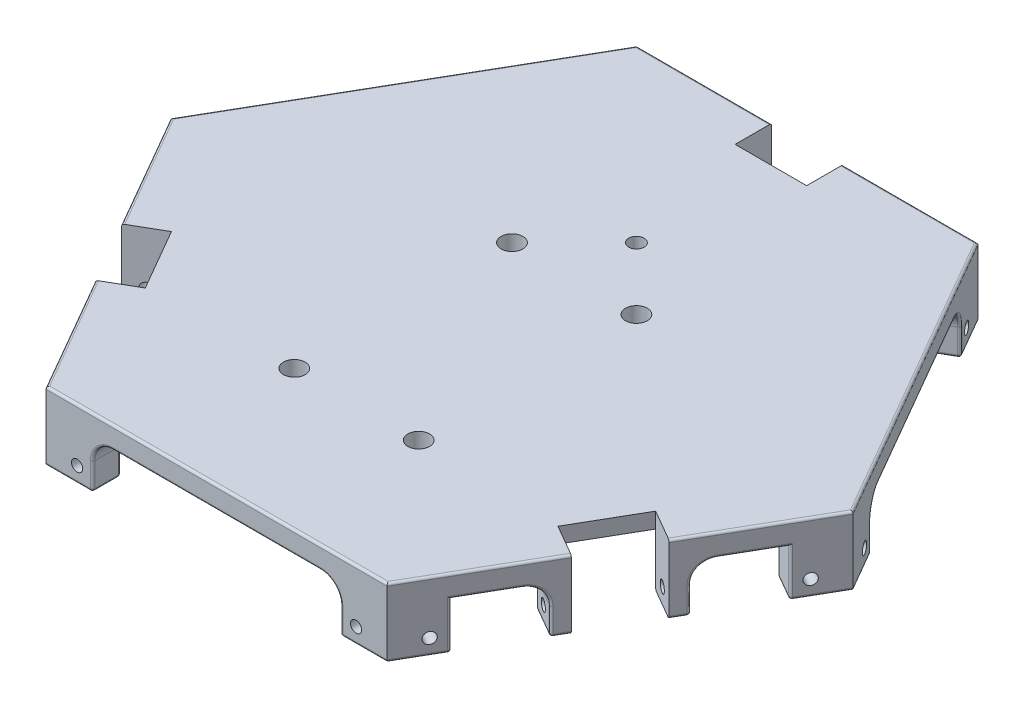
SolidWorks part; units mm, degrees
ref_plane "Plano frontal" through (0, 0, 0) normal (0, 0, 1) x (1, 0, 0)
ref_plane "Plano superior" through (0, 0, 0) normal (0, 1, 0) x (1, 0, 0)
ref_plane "Plano direito" through (0, 0, 0) normal (1, 0, 0) x (0, 0, -1)
sketch "Esboço1" plane through (0, 0, 0) normal (0, 1, 0) x (1, 0, 0)
  line L0 (-76.5224, -57.4593) -> (-54.8483, -95)
  line L1 (54.8483, 95) -> (11.5, 95)
  line L2 (-54.8483, 95) -> (-109.6966, 0)
  line L3 (-109.6966, 0) -> (-88.0224, -37.5407)
  line L4 (-54.8483, -95) -> (54.8483, -95)
  line L5 (54.8483, -95) -> (76.5224, -57.4593)
  line L6 (109.6966, 0) -> (54.8483, 95)
  line L7 (109.6966, 0) -> (54.8483, -95) construction
  line L8 (88.0224, -37.5407) -> (109.6966, 0)
  line L9 (-54.8483, -95) -> (-109.6966, 0) construction
  line L10 (-54.8483, 95) -> (54.8483, 95) construction
  line L11 (0, 95) -> (0, 0) construction
  line L12 (0, 0) -> (-82.2724, -47.5) construction
  line L13 (11.5, 95) -> (11.5, 83.25)
  line L14 (-11.5, 83.25) -> (11.5, 83.25)
  line L15 (-11.5, 83.25) -> (-11.5, 95)
  line L16 (82.2724, -47.5) -> (0, 0) construction
  line L18 (88.0224, -37.5407) -> (77.8466, -31.6657)
  line L19 (77.8466, -31.6657) -> (66.3466, -51.5843)
  line L20 (66.3466, -51.5843) -> (76.5224, -57.4593)
  line L23 (-76.5224, -57.4593) -> (-66.3466, -51.5843)
  line L24 (-66.3466, -51.5843) -> (-77.8466, -31.6657)
  line L25 (-77.8466, -31.6657) -> (-88.0224, -37.5407)
  line L28 (-11.5, 95) -> (-54.8483, 95)
  point P11 (72.0966, -41.625)
  point P12 (-72.0966, -41.625)
  point P13 (0, 83.25)
  dimension "D1" = 190
  dimension "D8" = 23
  dimension "D9" = 11.75
extrude "Ressalto-extrusão1" add sketch "Esboço1" along normal blind 3
sketch "Esboço3" plane through (0, 3, 0) normal (0, 1, 0) x (1, 0, 0)
  line L0 (-66.3466, -51.5843) -> (-60.2844, -48.0843)
  line L1 (-60.2844, -48.0843) -> (-63.2844, -42.8881)
  line L2 (-63.2844, -42.8881) -> (-69.3466, -46.3881)
  line L3 (-77.8466, -31.6657) -> (-66.3466, -51.5843) construction
  line L4 (-69.3466, -46.3881) -> (-66.3466, -51.5843)
  line L5 (-77.8466, -31.6657) -> (-71.7844, -28.1657)
  line L6 (-71.7844, -28.1657) -> (-68.7844, -33.3619)
  line L7 (-68.7844, -33.3619) -> (-74.8466, -36.8619)
  line L8 (-74.8466, -36.8619) -> (-77.8466, -31.6657)
  line L10 (-11.5, 83.25) -> (-11.5, 75.25)
  line L11 (-11.5, 75.25) -> (-5.5, 75.25)
  line L12 (-5.5, 75.25) -> (-5.5, 83.25)
  line L13 (11.5, 83.25) -> (-11.5, 83.25) construction
  line L14 (-5.5, 83.25) -> (-11.5, 83.25)
  line L15 (11.5, 83.25) -> (11.5, 75.25)
  line L16 (11.5, 75.25) -> (5.5, 75.25)
  line L17 (5.5, 75.25) -> (5.5, 83.25)
  line L18 (5.5, 83.25) -> (11.5, 83.25)
  line L19 (66.3466, -51.5843) -> (59.4184, -47.5843)
  line L20 (59.4184, -47.5843) -> (62.4184, -42.3881)
  line L21 (62.4184, -42.3881) -> (69.3466, -46.3881)
  line L22 (66.3466, -51.5843) -> (77.8466, -31.6657) construction
  line L23 (69.3466, -46.3881) -> (66.3466, -51.5843)
  line L24 (77.8466, -31.6657) -> (70.9184, -27.6657)
  line L25 (77.8466, -31.6657) -> (88.0224, -37.5407) construction
  line L26 (70.9184, -27.6657) -> (67.9184, -32.8619)
  line L27 (67.9184, -32.8619) -> (74.8466, -36.8619)
  line L28 (74.8466, -36.8619) -> (77.8466, -31.6657)
  dimension "D1" = 6
  dimension "D2" = 7
  dimension "D3" = 90
  dimension "D4" = 6
  dimension "D5" = 7
  dimension "D6" = 8
  dimension "D7" = 8
  dimension "D8" = 6
  dimension "D9" = 6
  dimension "D10" = 8
  dimension "D11" = 8
  dimension "D12" = 6
  dimension "D13" = 6
extrude "Ressalto-extrusão4" add sketch "Esboço3" against normal blind 0.0001
sketch "Sketch1" plane through (0, 3, 0) normal (0, 1, 0) x (1, 0, 0)
  line L0 (0, 83.5) -> (0, 75.25) construction
  line L1 (11.25, 83.5) -> (-11.25, 83.5) construction
  line L2 (3, 75.25) -> (-3, 75.25) construction
  line L3 (0, 0) -> (82.2724, 47.5) construction
  line L4 (109.6966, 0) -> (54.8483, 95) construction
  line L5 (0, 0) -> (-82.2724, 47.5) construction
  line L6 (-54.8483, 95) -> (-109.6966, 0) construction
  circle A0 centre (0, 79.375) radius 1.75
  circle A1 centre (68.7408, -39.6875) radius 1.75
  circle A2 centre (-68.7408, -39.6875) radius 1.75
  dimension "D1" = 3.5
extrude "Cut-Extrude1" [suppressed] cut sketch "Sketch1" against normal through all
sketch "Sketch5" plane through (0, 3, 0) normal (0, 1, 0) x (1, 0, 0)
  line L0 (77.8466, -31.6657) -> (88.0224, -37.5407) construction
  line L1 (88.0224, -37.5407) -> (109.6966, 0) construction
  line L2 (109.6966, 0) -> (54.8483, 95) construction
  line L3 (54.8483, 95) -> (11.5, 95) construction
  line L4 (11.5, 95) -> (11.5, 83.25) construction
  line L5 (-11.5, 83.25) -> (-11.5, 95) construction
  line L6 (-11.5, 95) -> (-54.8483, 95) construction
  line L7 (-54.8483, 95) -> (-109.6966, 0) construction
  line L8 (-109.6966, 0) -> (-88.0224, -37.5407) construction
  line L9 (-88.0224, -37.5407) -> (-77.8466, -31.6657) construction
  line L10 (-66.3466, -51.5843) -> (-76.5224, -57.4593) construction
  line L11 (-76.5224, -57.4593) -> (-54.8483, -95) construction
  line L12 (76.5224, -57.4593) -> (66.3466, -51.5843) construction
  line L13 (-54.8483, -95) -> (54.8483, -95) construction
  line L14 (54.8483, -95) -> (76.5224, -57.4593) construction
  line L15 (77.8466, -31.6657) -> (88.0224, -37.5407)
  line L16 (88.0224, -37.5407) -> (109.6966, 0)
  line L17 (109.6966, 0) -> (54.8483, 95)
  line L18 (54.8483, 95) -> (11.5, 95)
  line L19 (11.5, 95) -> (11.5, 83.25)
  line L20 (-11.5, 83.25) -> (-11.5, 95)
  line L21 (-11.5, 95) -> (-54.8483, 95)
  line L22 (-54.8483, 95) -> (-109.6966, 0)
  line L23 (-109.6966, 0) -> (-88.0224, -37.5407)
  line L24 (-88.0224, -37.5407) -> (-77.8466, -31.6657)
  line L25 (-66.3466, -51.5843) -> (-76.5224, -57.4593)
  line L26 (-76.5224, -57.4593) -> (-54.8483, -95)
  line L27 (76.5224, -57.4593) -> (66.3466, -51.5843)
  line L28 (-54.8483, -95) -> (54.8483, -95)
  line L29 (54.8483, -95) -> (76.5224, -57.4593)
  line L30 (82.3466, -23.8715) -> (84.7282, -25.2465)
  line L31 (84.7282, -25.2465) -> (99.3042, 0)
  line L32 (99.3042, 0) -> (49.6521, 86)
  line L33 (49.6521, 86) -> (20.5, 86)
  line L34 (20.5, 86) -> (20.5, 83.25)
  line L35 (-61.8466, -59.3785) -> (-64.2282, -60.7535)
  line L36 (-64.2282, -60.7535) -> (-49.6521, -86)
  line L37 (-49.6521, -86) -> (49.6521, -86)
  line L38 (49.6521, -86) -> (64.2282, -60.7535)
  line L39 (64.2282, -60.7535) -> (61.8466, -59.3785)
  line L40 (-20.5, 83.25) -> (-20.5, 86)
  line L41 (-20.5, 86) -> (-49.6521, 86)
  line L42 (-49.6521, 86) -> (-99.3042, 0)
  line L43 (-99.3042, 0) -> (-84.7282, -25.2465)
  line L44 (-84.7282, -25.2465) -> (-82.3466, -23.8715)
  line L45 (11.5, 83.25) -> (20.5, 83.25)
  line L46 (-11.5, 83.25) -> (-20.5, 83.25)
  line L47 (-82.3466, -23.8715) -> (-77.8466, -31.6657)
  line L48 (-66.3466, -51.5843) -> (-61.8466, -59.3785)
  line L49 (66.3466, -51.5843) -> (61.8466, -59.3785)
  line L50 (77.8466, -31.6657) -> (82.3466, -23.8715)
  dimension "D1" = 9
extrude "Boss-Extrude2" add sketch "Sketch5" against normal blind 5
sketch "Esboço4" plane through (0, -2, 0) normal (0, -1, 0) x (1, 0, 0)
  line L0 (-76.5224, 57.4593) -> (-74.0224, 61.7894)
  line L1 (-76.5224, 57.4593) -> (-54.8483, 95) construction
  line L2 (-74.0224, 61.7894) -> (-63.8466, 55.9144)
  line L3 (-63.8466, 55.9144) -> (-66.3466, 51.5843)
  line L4 (-66.3466, 51.5843) -> (-76.5224, 57.4593)
  line L5 (0, 0) -> (-72.0966, 41.625) construction
  line L6 (-77.8466, 31.6657) -> (-66.3466, 51.5843) construction
  line L7 (-77.8466, 31.6657) -> (-88.0224, 37.5407)
  line L8 (-80.3466, 27.3356) -> (-77.8466, 31.6657)
  line L9 (-90.5224, 33.2106) -> (-80.3466, 27.3356)
  line L10 (-88.0224, 37.5407) -> (-90.5224, 33.2106)
  line L11 (-76.5224, 57.4593) -> (-54.8483, 95) construction
  line L12 (-109.6966, 0) -> (-88.0224, 37.5407) construction
  line L13 (-88.0224, 37.5407) -> (-77.8466, 31.6657) construction
  dimension "D1" = 11.75
  dimension "D2" = 5
extrude "Ressalto-extrusão5" add sketch "Esboço4" along normal blind 15
sketch "Esboço5" plane through (-8.25, 0, -14.2894) normal (-0.5, 0, -0.866) x (-0.866, 0, 0.5)
  line L0 (95, -17) -> (83.25, -17) construction
  circle A0 centre (89.125, -12) radius 1.8
  dimension "D1" = 3.6
  dimension "D2" = 5
extrude "Corte-extrusão1" cut sketch "Esboço5" against normal blind 35 contours A0
ref_axis "Eixo1" through (0, 0, 0) along (0, -1, 0)
pattern_circular "PadrãoCircular1" count 3 over 360 about axis through (0, 0, 0) along (0, -1, 0) of "Ressalto-extrusão5", "Corte-extrusão1"
sketch "Esboço9" plane through (0, -2, 0) normal (0, -1, 0) x (1, 0, 0)
  line L0 (-54.8483, 95) -> (-39.8483, 95)
  line L1 (-54.8483, 95) -> (54.8483, 95) construction
  line L2 (-39.8483, 95) -> (-39.8483, 86)
  line L3 (-54.8483, 95) -> (-62.3483, 82.0096)
  line L5 (-62.3483, 82.0096) -> (-54.554, 77.5096)
  line L6 (-49.6521, 86) -> (-54.554, 77.5096)
  line L7 (-39.8483, 86) -> (-49.6521, 86)
  line L8 (54.8483, 95) -> (62.3483, 82.0096)
  line L10 (62.3483, 82.0096) -> (54.554, 77.5096)
  line L11 (54.554, 77.5096) -> (49.6521, 86)
  line L12 (54.8483, 95) -> (39.8483, 95)
  line L13 (39.8483, 95) -> (39.8483, 86)
  line L14 (39.8483, 86) -> (49.6521, 86)
  line L15 (109.6966, 0) -> (102.1966, 12.9904)
  line L17 (102.1966, 12.9904) -> (94.4023, 8.4904)
  line L18 (109.6966, 0) -> (102.1966, -12.9904)
  line L19 (109.6966, 0) -> (54.8483, -95) construction
  line L20 (102.1966, -12.9904) -> (94.4023, -8.4904)
  line L21 (94.4023, -8.4904) -> (99.3042, 0)
  line L22 (99.3042, 0) -> (94.4023, 8.4904)
  line L23 (54.8483, -95) -> (39.8483, -95)
  line L24 (54.8483, 95) -> (74.0224, 61.7894) construction
  line L26 (54.8483, -95) -> (62.3483, -82.0096)
  line L27 (62.3483, -82.0096) -> (54.554, -77.5096)
  line L28 (39.8483, -95) -> (39.8483, -86)
  line L29 (39.8483, -86) -> (49.6521, -86)
  line L30 (49.6521, -86) -> (54.554, -77.5096)
  line L31 (-54.8483, -95) -> (-62.3483, -82.0096)
  line L32 (-54.8483, -95) -> (-109.6966, 0) construction
  line L33 (-62.3483, -82.0096) -> (-54.554, -77.5096)
  line L34 (-54.8483, -95) -> (-39.8483, -95)
  line L36 (-39.8483, -95) -> (-39.8483, -86)
  line L37 (-39.8483, -86) -> (-49.6521, -86)
  line L38 (-49.6521, -86) -> (-54.554, -77.5096)
  line L39 (-54.554, -77.5096) -> (-54.4658, -78.0206)
  line L40 (-109.6966, 0) -> (-102.1966, 12.9904)
  line L42 (-102.1966, 12.9904) -> (-94.4023, 8.4904)
  line L43 (-94.4023, 8.4904) -> (-99.3042, 0)
  line L44 (-99.3042, 0) -> (-94.4023, -8.4904)
  line L45 (-94.4023, -8.4904) -> (-102.1966, -12.9904)
  line L46 (-102.1966, -12.9904) -> (-109.6966, 0)
  line L47 (-54.8483, 95) -> (54.8483, 95) construction
  dimension "D1" = 15
  dimension "D2" = 9
  dimension "D3" = 15
  dimension "D4" = 9
  dimension "D5" = 15
  dimension "D6" = 9
  dimension "D7" = 15
  dimension "D8" = 15
  dimension "D9" = 9
  dimension "D10" = 15
  dimension "D11" = 9
  dimension "D12" = 15
  dimension "D13" = 9.8038
  dimension "D14" = 15
  dimension "D15" = 9
  dimension "D16" = 9.8038
  dimension "D17" = 9.8038
extrude "Ressalto-extrusão8" add sketch "Esboço9" along normal blind 15 contours L15 L17 L22 L21 L20 L18 | L8 L10 L11 L14 L13 L12 | L7 L6 L5 L3 L0 L2 | L44 L45 L46 L40 L42 L43 | L38 L37 L36 L34 L31 L33 | L29 L30 L27 L26 L23 L28
sketch "Esboço10" plane through (0, 0, 95) normal (0, 0, 1) x (1, 0, 0)
  line L0 (54.8483, -17) -> (39.8483, -17) construction
  line L1 (39.8483, -17) -> (39.8483, -2) construction
  circle A0 centre (44.8483, -12) radius 1.8
  dimension "D1" = 5
  dimension "D2" = 5
  dimension "D3" = 3.6
extrude "Corte-extrusão2" cut sketch "Esboço10" against normal blind 216 and the other way blind 29
sketch "Esboço11" plane through (82.2724, 0, 47.5) normal (0.866, 0, 0.5) x (0.5, 0, -0.866)
  line L0 (-54.8483, -17) -> (-39.8483, -17) construction
  line L1 (-39.8483, -17) -> (-39.8483, -2) construction
  circle A0 centre (-44.8483, -12) radius 1.8026
  dimension "D1" = 5
  dimension "D2" = 5
extrude "Corte-extrusão3" cut sketch "Esboço11" against normal blind 216 and the other way blind 216
sketch "Esboço12" plane through (82.2724, 0, 47.5) normal (0.866, 0, 0.5) x (0.5, 0, -0.866)
  line L0 (54.8483, -17) -> (39.8483, -17) construction
  line L1 (39.8483, -17) -> (39.8483, -2) construction
  circle A0 centre (44.8483, -12) radius 1.804
  dimension "D1" = 5
  dimension "D2" = 5
extrude "Corte-extrusão4" cut sketch "Esboço12" against normal blind 216 and the other way blind 216
sketch "Esboço13" plane through (82.2724, 0, -47.5) normal (0.866, 0, -0.5) x (-0.5, 0, -0.866)
  line L0 (-39.8483, -17) -> (-39.8483, -2) construction
  line L1 (-54.8483, -17) -> (-39.8483, -17) construction
  circle A0 centre (-44.8483, -12) radius 1.8049
  dimension "D1" = 5
  dimension "D2" = 5
extrude "Corte-extrusão5" cut sketch "Esboço13" against normal blind 216 and the other way blind 216
sketch "Esboço14" plane through (82.2724, 0, -47.5) normal (0.866, 0, -0.5) x (-0.5, 0, -0.866)
  line L0 (39.8483, -17) -> (39.8483, -2) construction
  line L1 (54.8483, -17) -> (39.8483, -17) construction
  circle A0 centre (44.8483, -12) radius 1.8
  dimension "D1" = 3.6
  dimension "D2" = 5
  dimension "D3" = 5
extrude "Corte-extrusão6" cut sketch "Esboço14" against normal blind 216 and the other way blind 216
sketch "Esboço15" plane through (0, 0, -95) normal (0, 0, -1) x (-1, 0, 0)
  line L0 (39.8483, -17) -> (39.8483, -2) construction
  line L1 (54.8483, -17) -> (39.8483, -17) construction
  circle A0 centre (44.8483, -12) radius 1.8
  dimension "D1" = 5
  dimension "D2" = 5
  dimension "D3" = 3.6
extrude "Corte-extrusão7" cut sketch "Esboço15" against normal blind 216 and the other way blind 216
sketch "Sketch6" plane through (0, 3, 0) normal (0, 1, 0) x (1, 0, 0)
  line L18 (-77.8466, -31.6657) -> (-66.3466, -51.5843)
  line L19 (-66.3466, -51.5843) -> (-76.5224, -57.4593)
  line L20 (-76.5224, -57.4593) -> (-54.8483, -95)
  line L21 (-54.8483, -95) -> (54.8483, -95)
  line L22 (54.8483, -95) -> (76.5224, -57.4593)
  line L23 (76.5224, -57.4593) -> (66.3466, -51.5843)
  line L24 (66.3466, -51.5843) -> (77.8466, -31.6657)
  line L25 (77.8466, -31.6657) -> (88.0224, -37.5407)
  line L26 (88.0224, -37.5407) -> (109.6966, 0)
  line L27 (109.6966, 0) -> (54.8483, 95)
  line L28 (54.8483, 95) -> (11.5, 95)
  line L29 (11.5, 95) -> (11.5, 83.25)
  line L30 (11.5, 83.25) -> (-11.5, 83.25)
  line L31 (-11.5, 83.25) -> (-11.5, 95)
  line L32 (-11.5, 95) -> (-54.8483, 95)
  line L33 (-54.8483, 95) -> (-109.6966, 0)
  line L34 (-109.6966, 0) -> (-88.0224, -37.5407)
  line L35 (-88.0224, -37.5407) -> (-77.8466, -31.6657)
  line L36 (-77.8466, -31.6657) -> (-66.3466, -51.5843)
  line L37 (-66.3466, -51.5843) -> (-76.5224, -57.4593)
  line L38 (-76.5224, -57.4593) -> (-54.8483, -95)
  line L39 (-54.8483, -95) -> (54.8483, -95)
  line L40 (54.8483, -95) -> (76.5224, -57.4593)
  line L41 (76.5224, -57.4593) -> (66.3466, -51.5843)
  line L42 (66.3466, -51.5843) -> (77.8466, -31.6657)
  line L43 (77.8466, -31.6657) -> (88.0224, -37.5407)
  line L44 (88.0224, -37.5407) -> (109.6966, 0)
  line L45 (109.6966, 0) -> (54.8483, 95)
  line L46 (54.8483, 95) -> (11.5, 95)
  line L47 (11.5, 95) -> (11.5, 83.25)
  line L48 (11.5, 83.25) -> (-11.5, 83.25)
  line L49 (-11.5, 83.25) -> (-11.5, 95)
  line L50 (-11.5, 95) -> (-54.8483, 95)
  line L51 (-54.8483, 95) -> (-109.6966, 0)
  line L52 (-109.6966, 0) -> (-88.0224, -37.5407)
  line L53 (-88.0224, -37.5407) -> (-77.8466, -31.6657)
  dimension "D1" = 0
extrude "Boss-Extrude3" add sketch "Sketch6" along normal blind 2
fillet "Fillet1" radius 6.5 16 edges at (-85.4345, -2, 30.2731) (-98.2994, -2, 10.7404) (-98.2994, -2, -10.7404) (-58.4512, -2, -79.7596) (-39.8483, -2, -90.5) (-16.5, -2, -89.125) (58.4512, -2, -79.7596) (16.5, -2, -89.125) (39.8483, -2, -90.5) (98.2994, -2, -10.7404) (85.4345, -2, 30.2731) (-39.8483, -2, 90.5) (39.8483, -2, 90.5) (-58.4512, -2, 79.7596) (-68.9345, -2, 58.8519) (68.9345, -2, 58.8519)
fillet "Fillet2" radius 0.75 157 edges at (-102.1966, -12.75, 12.9904) (-101.2446, -3.9038, 14.6391) (-96.3595, -2, 23.1005) (-90.5224, -12.75, 33.2106) (-74.0224, -12.75, 61.7894) (-73.0705, -3.9038, 63.4382) (-62.3483, -12.75, 82.0096) (-63.3002, -3.9038, 80.3609) (102.1966, -12.75, -12.9904) (101.2446, -3.9038, -14.6391) (62.3483, -12.75, -82.0096) (63.3002, -3.9038, -80.3609) (39.8483, -12.75, -95) (37.9445, -3.9038, -95) (16.5, -12.75, -95) (18.4038, -3.9038, -95) (94.4023, -12.75, -8.4904) (93.4504, -3.9038, -10.1391) (74.4782, -2, -43) (55.5059, -3.9038, -75.8609) (39.8483, -12.75, -86) (37.9445, -3.9038, -86) (28.1741, -2, -86) (16.5, -12.75, -83.25) (-16.5, -12.75, -95) (-18.4038, -3.9038, -95) (-39.8483, -12.75, -95) (-37.9445, -3.9038, -95) (-39.8483, -12.75, -86) (-37.9445, -3.9038, -86) (-28.1741, -2, -86) (-16.5, -12.75, -83.25) (-62.3483, -12.75, -82.0096) (-63.3002, -3.9038, -80.3609) (-82.2724, -2, -47.5) (-102.1966, -12.75, -12.9904) (-94.4023, -12.75, -8.4904) (-54.554, -12.75, -77.5096) (-55.5059, -3.9038, -75.8609) (-74.4782, -2, -43) (-94.4023, -12.75, 8.4904) (-93.4504, -3.9038, 10.1391) (-88.5653, -2, 18.6005) (-80.3466, -12.75, 27.3356) (-63.8466, -12.75, 55.9144) (-54.554, -12.75, 77.5096) (-55.5059, -3.9038, 75.8609) (-63.6156, -2.1262, 61.8146) (39.8483, -12.75, 86) (-39.8483, -12.75, 86) (-37.9445, -3.9038, 86) (0, -2, 86) (63.6156, -2.1262, 61.8146) (63.3008, -4.8944, 56.8598) (80.8925, -4.8944, 26.3902) (90.5224, -12.75, 33.2106) (91.4743, -3.9038, 31.5618) (-39.8483, -12.75, 95) (-37.9445, -3.9038, 95) (0, -2, 95) (37.9445, -3.9038, 95) (66.5603, -2, 74.7141) (73.0705, -3.9038, 63.4382) (-44.7502, -17, 86) (-52.1031, -17, 81.7548) (-96.8533, -17, -4.2452) (-96.8533, -17, 4.2452) (44.7502, -17, -86) (52.1031, -17, -81.7548) (-52.1031, -17, -81.7548) (-44.7502, -17, -86) (96.8533, -17, -4.2452) (96.8533, -17, 4.2452) (52.1031, -17, 81.7548) (44.7502, -17, 86) (-91.4743, -3.9038, 31.5618) (-68.1853, -2, 71.8995) (82.2724, -2, -47.5) (28.1741, -2, -95) (54.554, -12.75, -77.5096) (21.7252, -2.1262, -86) (20.5, -2.5, -84.625) (17.5917, -4.8944, -83.25) (14, -17, -83.25) (-14, -17, -83.25) (-28.1741, -2, -95) (-20.5, -2.5, -84.625) (-21.7252, -2.1262, -86) (-17.5917, -4.8944, -83.25) (-101.2446, -3.9038, -14.6391) (-93.4504, -3.9038, -10.1391) (-85.3408, -2.1262, 24.1854) (-83.5374, -2.5, 24.559) (-80.8925, -4.8944, 26.3902) (-63.0374, -2.5, 60.066) (-63.3008, -4.8944, 56.8598) (-60.3911, -2, 67.3995) (37.9445, -3.9038, 86) (54.554, -9.5, 77.5096) (58.7661, -2, 70.2141) (63.0374, -2.5, 60.066) (63.8466, -12.75, 55.9144) (80.3466, -12.75, 27.3356) (62.3483, -9.5, 82.0096) (97.9845, -2, 20.2859) (102.1966, -9.5, 12.9904) (39.8483, -12.75, 95) (74.0224, -12.75, 61.7894) (-65.0966, -17, 53.7494) (-79.0966, -17, 29.5006) (65.0966, -17, 53.7494) (79.0966, -17, 29.5006) (-89.2724, -17, 35.3756) (-75.2724, -17, 59.6244) (-47.3483, -17, 95) (-58.5983, -17, 88.5048) (47.3483, -17, 95) (58.5983, -17, 88.5048) (75.2724, -17, 59.6244) (89.2724, -17, 35.3756) (105.9466, -17, 6.4952) (105.9466, -17, -6.4952) (58.5983, -17, -88.5048) (14, -17, -95) (-14, -17, -95) (47.3483, -17, -95) (-105.9466, -17, 6.4952) (-105.9466, -17, -6.4952) (-58.5983, -17, -88.5048) (-47.3483, -17, -95) (-98.8595, 5, 18.7704) (-65.6853, 5, 76.2296) (0, 5, 95) (65.6853, 5, 76.2296) (98.8595, 5, 18.7704) (82.2724, 5, -47.5) (33.1741, 5, -95) (-33.1741, 5, -95) (-82.2724, 5, -47.5) (-98.2994, -17, -10.7404) (-98.2994, -17, 10.7404) (-58.4512, -17, -79.7596) (-39.8483, -17, -90.5) (-16.5, -17, -89.125) (16.5, -17, -89.125) (39.8483, -17, -90.5) (58.4512, -17, -79.7596) (98.2994, -17, -10.7404) (98.2994, -17, 10.7404) (85.4345, -17, 30.2731) (68.9345, -17, 58.8519) (58.4512, -17, 79.7596) (39.8483, -17, 90.5) (-39.8483, -17, 90.5) (-58.4512, -17, 79.7596) (-68.9345, -17, 58.8519) (-85.4345, -17, 30.2731)
fillet "Fillet3" radius 0.75 21 edges at (16, 0, -83.25) (20.5, 0, -84.625) (35.0761, 0, -86) (-20.5, 0, -84.625) (-16, 0, -83.25) (-35.0761, 0, -86) (-74.4782, 0, -43) (-83.5374, 0, 24.559) (-92.0162, 0, 12.6232) (-80.0966, 0, 27.7686) (-63.0374, 0, 60.066) (-56.9402, 0, 73.3768) (-64.0966, 0, 55.4814) (63.0374, 0, 60.066) (0, 0, 86) (56.9402, 0, 73.3768) (64.0966, 0, 55.4814) (80.0966, 0, 27.7686) (83.5374, 0, 24.559) (74.4782, 0, -43) (92.0162, 0, 12.6232)
sketch "Esboço16" plane through (0, 5, 0) normal (0, 1, 0) x (1, 0, 0)
  line L0 (0, -51.4717) -> (0, 54.3752) construction
  line L1 (54.8483, -95) -> (-54.8483, -95) construction
  circle A0 centre (20, -50) radius 3.5
  circle A1 centre (20, 20) radius 3.5
  circle A2 centre (-20, 20) radius 3.5
  circle A3 centre (-20, -50) radius 3.5
  circle A4 centre (0, 40) radius 2.5
  dimension "D1" = 20
  dimension "D2" = 20
  dimension "D3" = 70
  dimension "D4" = 7
  dimension "D5" = 7
  dimension "D7" = 20
  dimension "D8" = 5
  dimension "D6" = 45
extrude "Corte-extrusão8" cut sketch "Esboço16" against normal blind 10
